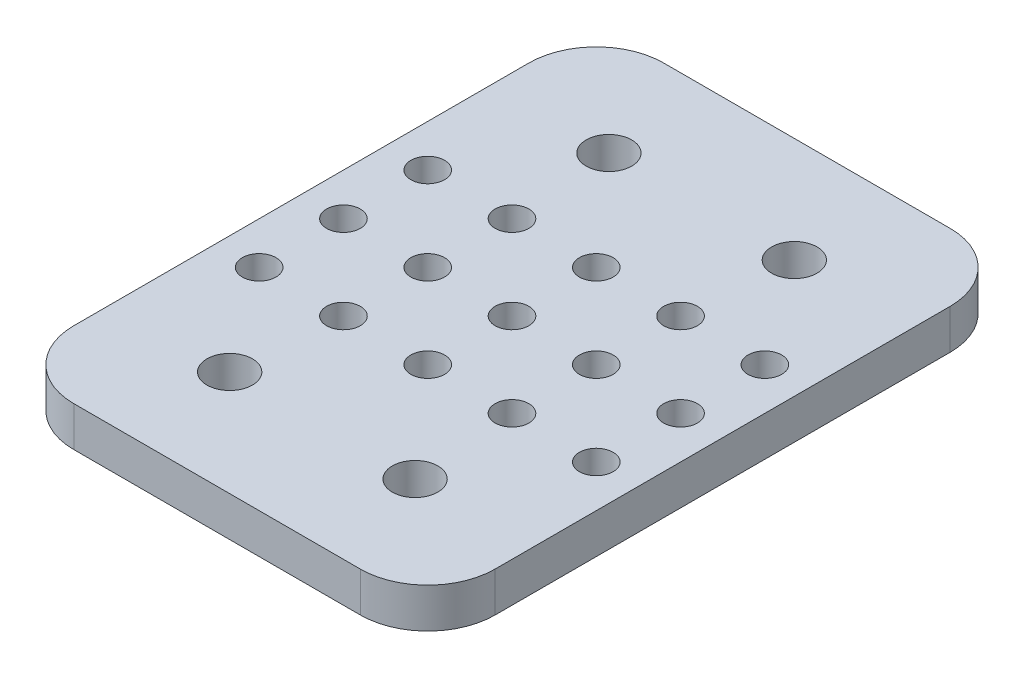
SolidWorks part; units mm, degrees
other "Markup1"
sketch "Sketch3" plane through (0, 6, 0) normal (-0.2556, 0.7181, 0.6473) x (0.9665, 0.2047, 0.1545)
sketch "Sketch5" plane through (0, 6, 0) normal (-0.2556, 0.7181, 0.6473) x (0.9665, 0.2047, 0.1545)
ref_plane "Front Plane" through (0, 0, 0) normal (0, 0, 1) x (1, 0, 0)
ref_plane "Top Plane" through (0, 0, 0) normal (0, 1, 0) x (1, 0, 0)
ref_plane "Right Plane" through (0, 0, 0) normal (1, 0, 0) x (0, 0, -1)
sketch "Sketch1" plane through (0, 0, 0) normal (0, 1, 0) x (1, 0, 0)
  line L0 (31.75, 88.9) -> (31.75, 0) construction
  line L1 (0, 0) -> (63.5, 0)
  line L2 (0, 0) -> (0, 88.9)
  line L3 (0, 88.9) -> (63.5, 88.9)
  line L4 (63.5, 0) -> (63.5, 88.9)
  circle A0 centre (17.78, 73.025) radius 3.429
  circle A1 centre (45.72, 15.875) radius 3.429
  circle A2 centre (17.78, 15.875) radius 3.429
  circle A3 centre (45.72, 73.025) radius 3.429
  dimension "D3" = 57.15
  dimension "D4" = 27.94
  dimension "D5" = 6.858
  dimension "D6" = 15.875
  dimension "D7" = 17.78
  dimension "D1" = 63.5
  dimension "D2" = 88.9
extrude "Boss-Extrude1" add sketch "Sketch1" along normal blind 6
fillet "Fillet1" radius 10.16 4 edges at (0, 3, -88.9) (63.5, 3, -88.9) (63.5, 3, 0) (0, 3, 0)
sketch "Sketch2" plane through (0, 6, 0) normal (0, 1, 0) x (1, 0, 0)
  line L0 (0, 78.74) -> (0, 10.16) construction
  line L1 (0, 19.05) -> (63.5, 19.05) construction
  line L2 (0, 19.05) -> (0, 69.85)
  line L3 (0, 69.85) -> (63.5, 69.85) construction
  line L4 (63.5, 19.05) -> (63.5, 69.85)
  line L5 (63.5, 10.16) -> (63.5, 78.74) construction
  line L6 (53.34, 88.9) -> (10.16, 88.9) construction
  line L7 (6.35, 31.75) -> (19.05, 31.75) construction
  circle A0 centre (6.35, 57.15) radius 2.54
  circle A1 centre (6.35, 44.45) radius 2.54
  circle A2 centre (6.35, 31.75) radius 2.54
  circle A3 centre (19.05, 31.75) radius 2.54
  circle A4 centre (19.05, 44.45) radius 2.54
  circle A5 centre (19.05, 57.15) radius 2.54
  circle A6 centre (31.75, 31.75) radius 2.54
  circle A7 centre (31.75, 44.45) radius 2.54
  circle A8 centre (31.75, 57.15) radius 2.54
  circle A9 centre (44.45, 31.75) radius 2.54
  circle A10 centre (44.45, 44.45) radius 2.54
  circle A11 centre (44.45, 57.15) radius 2.54
  circle A12 centre (57.15, 31.75) radius 2.54
  circle A13 centre (57.15, 44.45) radius 2.54
  circle A14 centre (57.15, 57.15) radius 2.54
  dimension "D3" = 5.08
  dimension "D4" = 12.7
  dimension "D5" = 12.7
  dimension "D6" = 12.7
  dimension "D7" = 6.35
  dimension "D1" = 50.8
  dimension "D2" = 19.05
  dimension "D9" = 12.7
  dimension "D8" = 5
extrude "Cut-Extrude1" cut sketch "Sketch2" against normal through all contours A2 | A1 | A0 | A5 | A4 | A3 | A6 | A7 | A8 | A11 | A10 | A13 | A12 | A9 | A14 region at (6.35, 6, -57.15) region at (6.35, 6, -44.45) region at (6.35, 6, -31.75) region at (19.05, 6, -31.75) region at (19.05, 6, -44.45) region at (19.05, 6, -57.15) region at (31.75, 6, -31.75) region at (31.75, 6, -44.45) region at (31.75, 6, -57.15) region at (44.45, 6, -31.75) region at (44.45, 6, -44.45) region at (44.45, 6, -57.15) region at (57.15, 6, -31.75) region at (57.15, 6, -44.45)
sketch "Sketch4" plane through (0, 0, 0) normal (0, -1, 0) x (-1, 0, 0)
  line L0 (-1000, 0) -> (49000, 0) construction
  line L2 (-63.5, -1000) -> (-63.5, 49000) construction
  line L3 (-63.5, 10.16) -> (-63.5, 78.74) construction
  point P6 (-63.5, 0)
